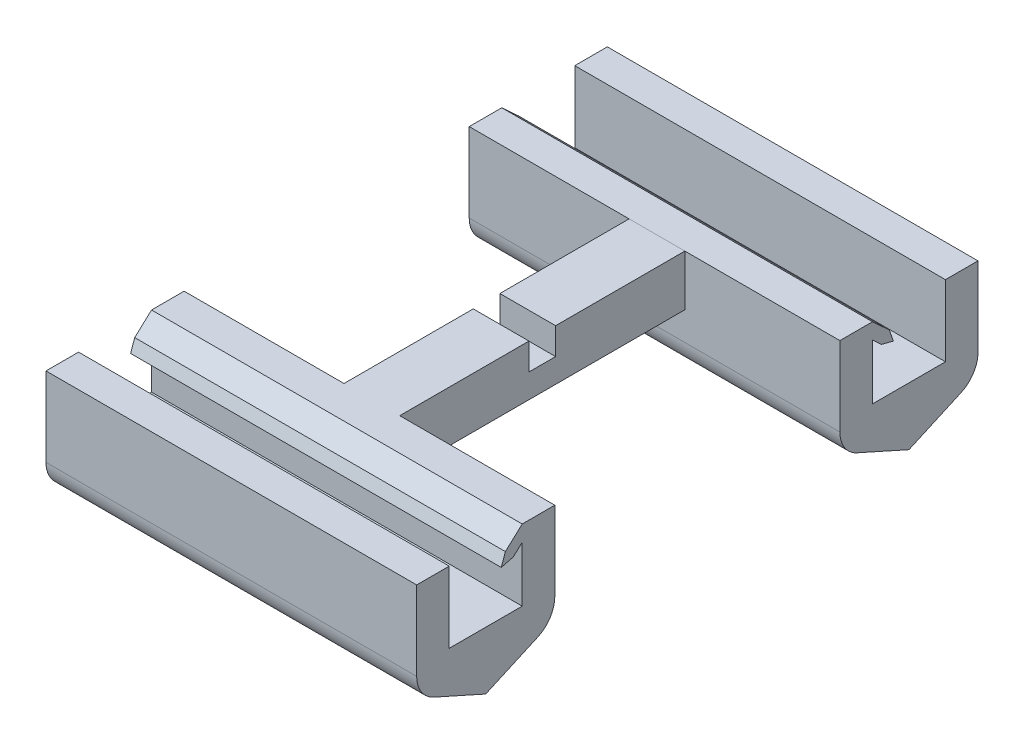
SolidWorks part; units mm, degrees
ref_plane "Front Plane" through (0, 0, 0) normal (0, 0, 1) x (1, 0, 0)
ref_plane "Top Plane" through (0, 0, 0) normal (0, 1, 0) x (1, 0, 0)
ref_plane "Right Plane" through (0, 0, 0) normal (1, 0, 0) x (0, 0, -1)
sketch "Sketch1" plane through (0, 0, 0) normal (1, 0, 0) x (0, 0, -1)
  line L0 (0, 0) -> (0, 50000) construction
  line L1 (6, -0.5435) -> (6, 0) construction
  line L2 (6.717, -0.9314) -> (6.4415, -0.6779) construction
  line L3 (6.5769, -0.5307) -> (6.3061, -0.8251) construction
  line L4 (6.3061, -0.8251) -> (6, -0.5435)
  line L5 (6.717, -0.9314) -> (6.3061, -0.8251)
  line L6 (6.5769, -0.5307) -> (6.717, -0.9314)
  line L7 (6, 0) -> (6.5769, -0.5307)
  line L8 (4.8841, 0) -> (4.8841, -2.7135)
  line L9 (5.4755, -3.6262) -> (7.25, -4.4206)
  line L10 (7.25, -1.3683) -> (7.25, 49998.6317) construction
  line L11 (-7.25, -1.3683) -> (-7.25, 49998.6317) construction
  line L12 (-6, 0) -> (-4.8841, 0)
  line L13 (-6, -2.4374) -> (-6, -0.5435)
  line L14 (-8.5, -2.4374) -> (-6, -2.4374)
  line L15 (-9.0245, -3.6262) -> (-7.25, -4.4206)
  line L16 (-9.6159, 0) -> (-9.6159, -2.7135)
  line L17 (-8.5, -2.4374) -> (-8.5, 0)
  line L18 (-8.5, 0) -> (-9.6159, 0)
  line L19 (-5.4755, -3.6262) -> (-7.25, -4.4206)
  line L20 (-4.8841, 0) -> (-4.8841, -2.7135)
  line L21 (-6, 0) -> (-6.5769, -0.5307)
  line L22 (-6.5769, -0.5307) -> (-6.717, -0.9314)
  line L23 (-6.717, -0.9314) -> (-6.3061, -0.8251)
  line L24 (-6.3061, -0.8251) -> (-6, -0.5435)
  line L25 (-6.5769, -0.5307) -> (-6.3061, -0.8251) construction
  line L26 (-6.717, -0.9314) -> (-6.4415, -0.6779) construction
  line L27 (-6, -0.5435) -> (-6, 0) construction
  line L28 (8.5, 0) -> (9.6159, 0)
  line L29 (8.5, -2.4374) -> (8.5, 0)
  line L30 (9.6159, 0) -> (9.6159, -2.7135)
  line L31 (9.0245, -3.6262) -> (7.25, -4.4206)
  line L32 (8.5, -2.4374) -> (6, -2.4374)
  line L33 (6, -2.4374) -> (6, -0.5435)
  line L34 (6, 0) -> (4.8841, 0)
  arc A0 (-5.4755, -3.6262) -> (-4.8841, -2.7135) centre (-5.8841, -2.7135) ccw
  arc A1 (-9.0245, -3.6262) -> (-9.6159, -2.7135) centre (-8.6159, -2.7135) cw
  arc A2 (9.0245, -3.6262) -> (9.6159, -2.7135) centre (8.6159, -2.7135) ccw
  arc A3 (5.4755, -3.6262) -> (4.8841, -2.7135) centre (5.8841, -2.7135) cw
  point P27 (-4.8841, -3.3614)
  point P35 (-6, -0.4524)
  point P45 (4.8841, -3.3614)
  dimension "D3" = 1
  dimension "D1" = 12
  dimension "D4" = 0.4
extrude "Boss-Extrude1" add sketch "Sketch1" along normal blind 12.7
sketch "Sketch2" plane through (0, 0, -4.8841) normal (0, 0, 1) x (1, 0, 0)
  line L1 (5.4781, 0) -> (7.3878, 0)
  line L2 (5.4781, 0) -> (5.4781, -1.7417)
  line L3 (5.4781, -1.7417) -> (7.3878, -1.7417) construction
  line L4 (7.3878, 0) -> (7.3878, -1.7417)
  line L5 (5.4781, -1.7417) -> (6.433, -2.6965)
  line L6 (6.433, -2.6965) -> (7.3878, -1.7417)
  line L7 (12.7, 0) -> (0, 0) construction
extrude "Boss-Extrude2" add sketch "Sketch2" along normal up to next
sketch "Sketch3" plane through (5.4781, 0, 0) normal (-1, 0, 0) x (0, 0, 1)
  line L0 (0, 0) -> (0, -50000) construction
  line L1 (4.8841, 0) -> (-4.8841, 0) construction
  line L2 (0.456, -0.9172) -> (0.456, 0)
  line L3 (-0.456, -0.9172) -> (-0.456, 0)
  line L4 (-0.456, 0) -> (0.456, 0)
  line L5 (0.456, -0.9172) -> (-0.456, -0.9172)
  point P4 (0, 0)
  dimension "D1" = 0.912
extrude "Cut-Extrude1" cut sketch "Sketch3" against normal up to next (1.9097 mm away)
